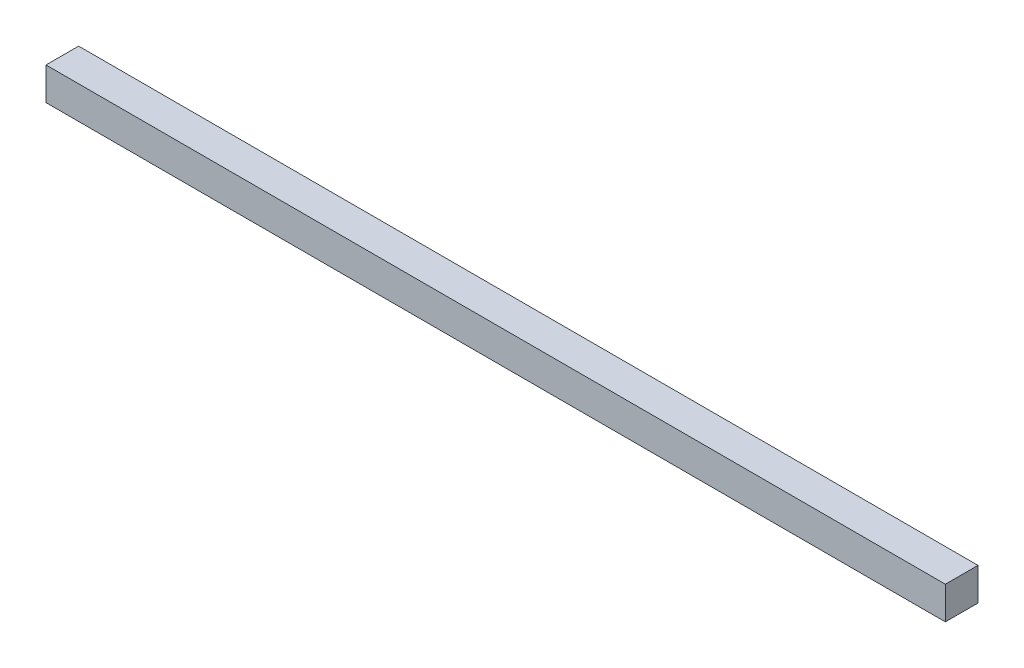
SolidWorks part; units mm, degrees
ref_plane "Front Plane" through (0, 0, 0) normal (0, 0, 1) x (1, 0, 0)
ref_plane "Top Plane" through (0, 0, 0) normal (0, 1, 0) x (1, 0, 0)
ref_plane "Right Plane" through (0, 0, 0) normal (1, 0, 0) x (0, 0, -1)
sketch "Sketch1" plane through (0, 0, 0) normal (0, 0, 1) x (1, 0, 0)
  line L0 (-124, 0) -> (124, 0) construction
  dimension "D1" = 248
sketch "Sketch2" plane through (0, 0, 0) normal (1, 0, 0) x (0, 0, -1)
  line L1 (-4.5, -4.5) -> (4.5, -4.5)
  line L2 (-4.5, -4.5) -> (-4.5, 4.5)
  line L3 (-4.5, 4.5) -> (4.5, 4.5)
  line L4 (4.5, -4.5) -> (4.5, 4.5)
  line L5 (-4.5, -4.5) -> (4.5, 4.5) construction
  line L6 (-4.5, 4.5) -> (4.5, -4.5) construction
  point P0 (0, 0)
  dimension "D1" = 9
extrude "Boss-Extrude1" add sketch "Sketch2" against normal up to vertex (124 mm away) and the other way up to vertex (124 mm away) up to point (-124, 0, 0) other way up to point (124, 0, 0)
